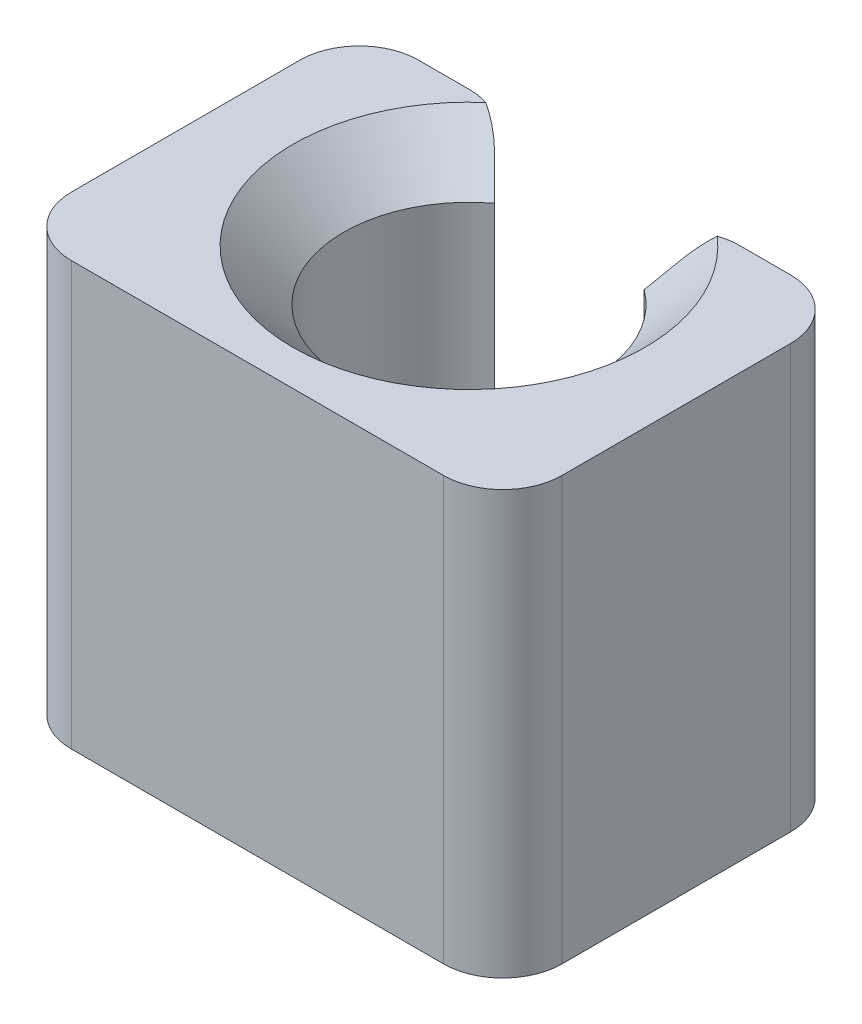
SolidWorks part; units mm, degrees
ref_plane "Front Plane" through (0, 0, 0) normal (0, 0, 1) x (1, 0, 0)
ref_plane "Top Plane" through (0, 0, 0) normal (0, 1, 0) x (1, 0, 0)
ref_plane "Right Plane" through (0, 0, 0) normal (1, 0, 0) x (0, 0, -1)
sketch "Sketch2" plane through (0, 0, 0) normal (0, 1, 0) x (1, 0, 0)
  line L1 (14.5, -12.5) -> (-14.5, -12.5)
  line L2 (14.5, -12.5) -> (14.5, 12.5)
  line L3 (14.5, 12.5) -> (-14.5, 12.5)
  line L4 (-14.5, -12.5) -> (-14.5, 12.5)
  line L5 (14.5, -12.5) -> (-14.5, 12.5) construction
  line L6 (14.5, 12.5) -> (-14.5, -12.5) construction
  circle A0 centre (0, 0) radius 6.1
  point P0 (0, 0)
  dimension "D3" = 12.2
  dimension "D1" = 29
  dimension "D2" = 25
extrude "Boss-Extrude2" add sketch "Sketch2" along normal blind 25
sketch "Sketch3" plane through (0, 25, 0) normal (0, 1, 0) x (1, 0, 0)
  circle A0 centre (0, 0) radius 7.4
  dimension "D1" = 14.8
extrude "Cut-Extrude1" cut sketch "Sketch3" against normal blind 15
sketch "Sketch4" plane through (0, 25, 0) normal (0, 1, 0) x (1, 0, 0)
  line L10 (-3.4884, 5.0041) -> (-6.5, 8.0157)
  line L11 (-6.5, 8.0157) -> (-14.5, 8.0157)
  line L12 (-14.5, 12.5) -> (-14.5, -12.5) construction
  line L13 (-14.5, 8.0157) -> (-14.5, 12.5)
  line L14 (-14.5, 12.5) -> (14.5, 12.5)
  line L15 (14.5, 12.5) -> (-14.5, 12.5) construction
  line L16 (14.5, 12.5) -> (14.5, 8.0157)
  line L17 (14.5, -12.5) -> (14.5, 12.5) construction
  line L18 (14.5, 8.0157) -> (6.5, 8.0157)
  line L19 (6.5, 8.0157) -> (3.4884, 5.0041)
  line L20 (3.4884, 5.0041) -> (-3.4884, 5.0041)
  circle A0 centre (0, 0) radius 6.1 construction
  dimension "D1" = 135
  dimension "D2" = 8
extrude "Cut-Extrude2" cut sketch "Sketch4" against normal through all
chamfer "Chamfer2" distance 3 angle 45 1 edges at (0, 25, 7.4)
chamfer "Chamfer4" distance 1.3 angle 45 1 edges at (0, 10, 6.1) tangent propagation no
fillet "Fillet1" radius 3.5 6 edges at (6.5, 12.46, -8.0157) (-6.5, 12.46, -8.0157) (14.5, 12.5, -8.0157) (14.5, 12.5, 12.5) (-14.5, 12.5, 12.5) (-14.5, 12.5, -8.0157)
